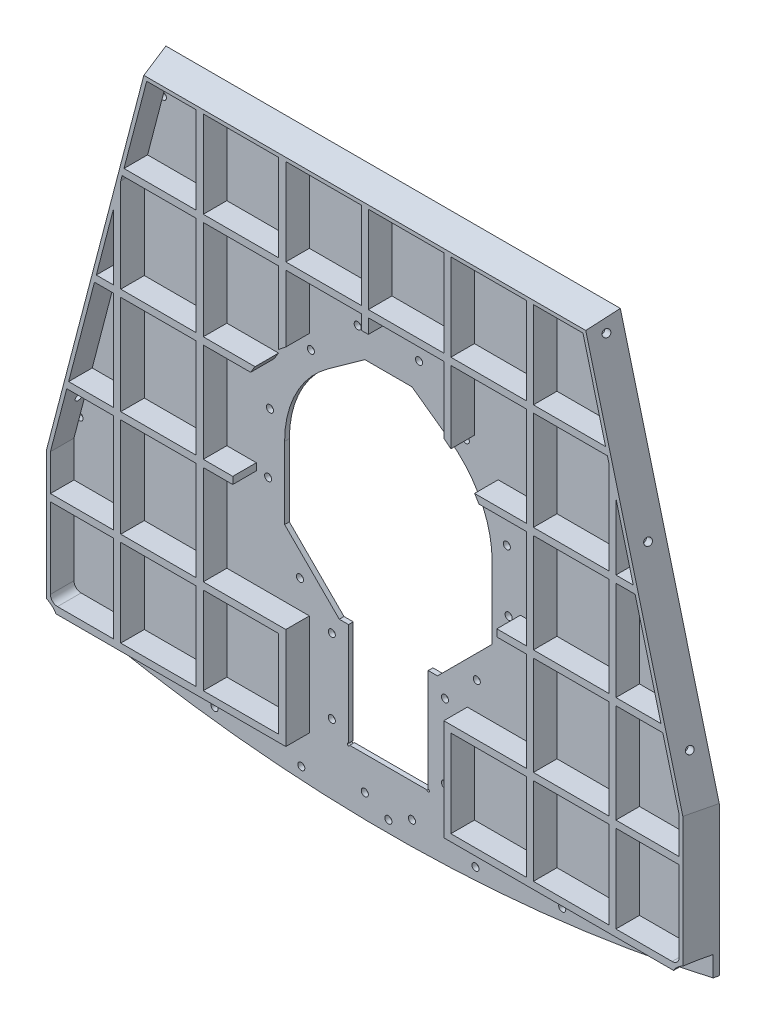
SolidWorks part; units mm, degrees
material "ABS"
ref_plane "前视基准面" through (0, 0, 0) normal (0, 0, 1) x (1, 0, 0)
ref_plane "上视基准面" through (0, 0, 0) normal (0, 1, 0) x (1, 0, 0)
ref_plane "右视基准面" through (0, 0, 0) normal (1, 0, 0) x (0, 0, -1)
other "Configuration Table"
sketch "草图1" plane through (0, 0, 0) normal (0, 0, 1) x (1, 0, 0)
  line L0 (145, -15) -> (145, -95)
  line L1 (145, -95) -> (-145, -95)
  line L2 (-145, -95) -> (-145, -15)
  line L3 (-145, -15) -> (-85, 215)
  line L4 (-85, 215) -> (85, 215)
  line L5 (85, 215) -> (145, -15)
  line L6 (0, 215) -> (0, -95) construction
  arc A0 (145, -95) -> (-145, -95) centre (0, 951.25) cw construction
  point P11 (0, -105)
  dimension "D4" = 320
  dimension "D1" = 10
  dimension "D2" = 290
  dimension "D3" = 80
  dimension "D5" = 170
  dimension "D6" = 95
extrude "凸台-拉伸1" add sketch "草图1" against normal blind 60
chamfer "倒角1" distance 20 distance2 60 4 edges at (115, 100, -60) (145, -55, -60) (-115, 100, -60) (-145, -55, -60)
sketch "草图2" plane through (0, 0, 0) normal (1, 0, 0) x (0, 0, -1)
  line L0 (10, 215) -> (0, 145)
  line L1 (60, 215) -> (0, 215) construction
  line L2 (0, 215) -> (0, -15) construction
  line L3 (0, 145) -> (0, 215)
  line L4 (0, 215) -> (10, 215)
  dimension "D1" = 70
  dimension "D2" = 10
extrude "切除-拉伸1" cut sketch "草图2" against normal through all and the other way through all
chamfer "倒角2" distance 20 distance2 60 1 edges at (0, 215, -60)
sketch "草图16" plane through (0, 0, -60) normal (0, 0, -1) x (-1, 0, 0)
  line L1 (-198.0208, 219.8054) -> (198.0208, 219.8054)
  line L2 (-198.0208, 219.8054) -> (-198.0208, -219.8054)
  line L3 (-198.0208, -219.8054) -> (198.0208, -219.8054)
  line L4 (198.0208, 219.8054) -> (198.0208, -219.8054)
  line L5 (-198.0208, 219.8054) -> (198.0208, -219.8054) construction
  line L6 (-198.0208, -219.8054) -> (198.0208, 219.8054) construction
  point P0 (0, 0)
extrude "切除-拉伸14" cut sketch "草图16" against normal offset from surface (58 mm away) 2 up to face at (0, 11.6667, 0)
sketch "草图17" plane through (0, 0, -2) normal (0, 0, -1) x (-1, 0, 0)
  line L15 (-138.3333, -89) -> (-138.3333, -99)
  line L17 (103.2609, 145) -> (-103.2609, 145) construction
  line L18 (96.3711, 145) -> (-96.3711, 145)
  line L19 (-138.3333, -99) -> (138.3333, -99)
  line L20 (93.114, 157.4855) -> (138.3333, -15.8553)
  line L21 (-138.3333, -15.8553) -> (-93.114, 157.4855)
  line L22 (138.3333, -15.8553) -> (138.3333, -89)
  line L23 (-138.3333, -89) -> (-138.3333, -15.8553)
  line L24 (138.3333, -89) -> (-138.3333, -89)
  line L25 (96.3711, 145) -> (138.3333, -15.8553)
  line L26 (-138.3333, -15.8553) -> (-96.3711, 145)
  line L27 (138.3333, -15.8553) -> (138.3333, -89)
  line L28 (-138.3333, -89) -> (-138.3333, -15.8553)
  line L29 (138.3333, -89) -> (-138.3333, -89) construction
  line L30 (138.3333, -99) -> (138.3333, -89)
  dimension "D2" = 10
  dimension "D1" = 6
extrude "切除-拉伸15" cut sketch "草图17" against normal blind 5 flip side to cut
sketch "草图19" plane through (0, 0, 0) normal (0, 0, 1) x (1, 0, 0)
  line L0 (0, 145) -> (0, -95) construction
  line L1 (-96.3711, 145) -> (96.3711, 145) construction
  line L2 (-138.3333, -95) -> (138.3333, -95) construction
  line L3 (-138.3333, -95) -> (-138.3333, -15.8553) construction
  line L4 (138.3333, -15.8553) -> (138.3333, -95) construction
  line L5 (-138.3333, -79.1076) -> (138.3333, -79.1076) construction
  line L6 (-138.3333, -79.1076) -> (-138.3333, -95)
  line L7 (-138.3333, -95) -> (138.3333, -95)
  line L8 (138.3333, -95) -> (138.3333, -79.1076)
  line L9 (-36.9344, -88.8716) -> (0, 515) construction
  line L10 (130.971, -7.4412) -> (128.3333, 2.67) construction
  line L11 (128.3333, 2.67) -> (128.3333, -79.1076) construction
  line L13 (96.3711, 145) -> (91.533, 143.7379) construction
  line L14 (130.971, -7.4412) -> (113.3015, 60.292) construction
  line L15 (113.3015, 60.292) -> (95.632, 128.0252) construction
  line L16 (95.632, 128.0252) -> (91.533, 143.7379) construction
  line L17 (96.3711, 145) -> (138.3333, -15.8553) construction
  line L18 (138.3333, -15.8553) -> (128.3333, -18.4639) construction
  line L19 (-44, 27) -> (-44, -3.5784)
  line L20 (-44, -3.5784) -> (-20.8284, -26.75)
  line L21 (-20.8284, -26.75) -> (-16.9, -26.75)
  line L23 (-16.9, -70.85) -> (16.9, -70.85)
  line L24 (16.9, -70.85) -> (16.9, -26.75)
  line L25 (16.9, -26.75) -> (20.8284, -26.75)
  line L26 (20.8284, -26.75) -> (44, -3.5784)
  line L27 (44, -3.5784) -> (44, 27)
  line L29 (-56, 27) -> (-56, -8.549) construction
  line L30 (-56, -8.549) -> (-29, -35.549) construction
  line L31 (-29, -35.549) -> (-29, -90) construction
  line L32 (-29, -90) -> (29, -90) construction
  line L33 (29, -90) -> (29, -35.549) construction
  line L34 (29, -35.549) -> (56, -8.549) construction
  line L35 (56, -8.549) -> (56, 27) construction
  line L37 (-56, 27) -> (56, 27) construction
  line L39 (-16.9, -26.75) -> (-16.9, -70.85)
  line L41 (43, 27) -> (43, -1.75) construction
  line L42 (43, -1.75) -> (20, -24.75) construction
  line L43 (20, -24.75) -> (-20, -24.75) construction
  line L44 (-20, -24.75) -> (-43, -1.75) construction
  line L45 (-43, -1.75) -> (-43, 27) construction
  line L47 (-25.682, 62.7272) -> (-10, 74)
  line L48 (-10, 74) -> (10, 74)
  line L49 (10, 74) -> (25.682, 62.7272)
  line L50 (-38.5777, 67.5926) -> (-15, 90) construction
  line L51 (-15, 90) -> (15, 90) construction
  line L52 (15, 90) -> (38.5777, 67.5926) construction
  line L53 (-24, -33.4779) -> (-24, -90) construction
  line L54 (-51, -6.4779) -> (-24, -33.4779) construction
  line L55 (-51, 27) -> (-51, -6.4779) construction
  line L56 (-35.1333, 63.9683) -> (-13.0031, 85) construction
  line L57 (-13.0031, 85) -> (13.0031, 85) construction
  line L58 (13.0031, 85) -> (35.1333, 63.9683) construction
  line L59 (51, -6.4779) -> (51, 27) construction
  line L60 (24, -33.4779) -> (51, -6.4779) construction
  line L61 (24, -90) -> (24, -33.4779) construction
  line L62 (-32.8449, 66.143) -> (0, 27) construction
  line L63 (0, 27) -> (-50.2252, 35.8561) construction
  arc A0 (-138.3333, -79.1076) -> (138.3333, -79.1076) centre (0, 515) ccw
  circle A4 centre (0, -90) radius 1.5
  circle A8 centre (95.632, 128.0252) radius 1.5
  circle A9 centre (113.3015, 60.292) radius 1.5
  circle A10 centre (130.971, -7.4412) radius 1.5
  circle A11 centre (40, 135) radius 1.5
  circle A12 centre (-40, 135) radius 1.5
  circle A16 centre (-130.971, -7.4412) radius 1.5
  circle A17 centre (-113.3015, 60.292) radius 1.5
  circle A18 centre (-95.632, 128.0252) radius 1.5
  circle A24 centre (0, -90) radius 3 construction
  circle A26 centre (0, 515) radius 605 construction
  circle A27 centre (-36.9344, -88.8716) radius 1.5
  circle A28 centre (-73.731, -85.4904) radius 1.5
  circle A29 centre (-110.2525, -79.8692) radius 1.5
  circle A30 centre (36.9344, -88.8716) radius 1.5
  circle A31 centre (73.731, -85.4904) radius 1.5
  circle A32 centre (110.2525, -79.8692) radius 1.5
  arc A33 (44, 27) -> (25.682, 62.7272) centre (0, 27) ccw
  arc A35 (56, 27) -> (38.5777, 67.5926) centre (0, 27) ccw construction
  circle A36 centre (0, 27) radius 43 construction
  arc A37 (-25.682, 62.7272) -> (-44, 27) centre (0, 27) ccw
  arc A38 (-38.5777, 67.5926) -> (-56, 27) centre (0, 27) ccw construction
  arc A39 (-35.1333, 63.9683) -> (-51, 27) centre (0, 27) ccw construction
  arc A40 (51, 27) -> (35.1333, 63.9683) centre (0, 27) ccw construction
  circle A41 centre (-13.0031, 85) radius 1.5
  circle A42 centre (-32.8449, 66.143) radius 1.5
  circle A43 centre (-50.2252, 35.8561) radius 1.5
  circle A44 centre (-51, 10.261) radius 1.5
  circle A45 centre (-37.5, -19.9779) radius 1.5
  circle A46 centre (-24, -33.4779) radius 1.5
  circle A47 centre (-24, -65) radius 1.5
  circle A48 centre (-10, -85) radius 1.5
  circle A49 centre (10, -85) radius 1.5
  circle A50 centre (24, -65) radius 1.5
  circle A51 centre (24, -33.4779) radius 1.5
  circle A52 centre (37.5, -19.9779) radius 1.5
  circle A53 centre (51, 10.261) radius 1.5
  circle A54 centre (50.2252, 35.8561) radius 1.5
  circle A55 centre (32.8449, 66.143) radius 1.5
  circle A56 centre (13.0031, 85) radius 1.5
  point P48 (0, 515)
  point P50 (0, 515)
  point P69 (0, -90)
  point P70 (0, -70.85)
  dimension "D2" = 3
  dimension "D7" = 70
  dimension "D9" = 80
  dimension "D11" = 12
  dimension "D17" = 40
  dimension "D20" = 610
  dimension "D21" = 5
  dimension "D22" = 4
  dimension "D23" = 6
  dimension "D24" = 51.75
  dimension "D15" = 44.1
  dimension "D19" = 45
  dimension "D27" = 3
  dimension "D1" = 88
  dimension "D10" = 58
  dimension "D12" = 56
  dimension "D16" = 86
  dimension "D26" = 20
  dimension "D29" = 7
  dimension "D31" = 3
  dimension "D32" = 5
  dimension "D33" = 20
  dimension "D34" = 10
  dimension "D3" = 3.5
  dimension "D4" = 5
  dimension "D5" = 10
  dimension "D6" = 10
  dimension "D8" = 10
  dimension "D13" = 117
  dimension "D14" = 33.8
  dimension "D18" = 2
  dimension "D25" = 2
  dimension "D28" = 30
  dimension "D30" = 5
  dimension "D35" = 40
  dimension "D36" = 80
extrude "切除-拉伸17" cut sketch "草图19" against normal blind 3
sketch "草图21" plane through (0, 0, 0) normal (0, 0, 1) x (1, 0, 0)
  circle A0 centre (-16.9, -70.85) radius 0.5
  circle A1 centre (16.9, -70.85) radius 0.5
  dimension "D1" = 1
extrude "切除-拉伸19" cut sketch "草图21" against normal blind 10
sketch "草图22" plane through (0, 0, 0) normal (0, 0, 1) x (1, 0, 0)
  line L0 (-96.3711, 145) -> (96.3711, 145) construction
  line L1 (1.5, -74.8692) -> (-1.5, -74.8692)
  line L2 (1.5, -74.8692) -> (1.5, 140)
  line L3 (1.5, 140) -> (-1.5, 140)
  line L4 (-1.5, -74.8692) -> (-1.5, 140)
  line L5 (1.5, -74.8692) -> (-1.5, 140) construction
  line L6 (1.5, 140) -> (-1.5, -74.8692) construction
  line L7 (36.5, -74.8692) -> (36.5, 140)
  line L8 (0, 145) -> (0, -95) construction
  line L9 (-138.3333, -79.1076) -> (-138.3333, -15.8553) construction
  line L10 (-138.3333, -71.8692) -> (138.3333, -71.8692)
  line L11 (-138.3333, -71.8692) -> (-138.3333, -74.8692)
  line L12 (-138.3333, -74.8692) -> (138.3333, -74.8692)
  line L13 (138.3333, -71.8692) -> (138.3333, -74.8692)
  line L14 (-138.3333, -71.8692) -> (138.3333, -74.8692) construction
  line L15 (-138.3333, -74.8692) -> (138.3333, -71.8692) construction
  line L16 (138.3333, -15.8553) -> (138.3333, -79.1076) construction
  line L17 (36.5, -74.8692) -> (33.5, -74.8692)
  line L18 (33.5, -74.8692) -> (33.5, 140)
  line L19 (36.5, 140) -> (33.5, 140)
  line L20 (71.5, -74.8692) -> (71.5, 140)
  line L21 (71.5, -74.8692) -> (68.5, -74.8692)
  line L22 (68.5, -74.8692) -> (68.5, 140)
  line L23 (71.5, 140) -> (68.5, 140)
  line L24 (106.5, -74.8692) -> (106.5, 140)
  line L25 (106.5, -74.8692) -> (103.5, -74.8692)
  line L26 (103.5, -74.8692) -> (103.5, 140)
  line L27 (106.5, 140) -> (103.5, 140)
  line L40 (96.3711, 145) -> (138.3333, -15.8553)
  line L41 (96.3711, 145) -> (91.533, 143.7379)
  line L42 (138.3333, -15.8553) -> (133.4952, -17.1174)
  line L43 (91.533, 143.7379) -> (133.4952, -17.1174)
  line L44 (138.3333, -79.1076) -> (138.3333, -15.8553)
  line L45 (138.3333, -79.1076) -> (133.3333, -79.1076)
  line L46 (138.3333, -15.8553) -> (133.3333, -15.8553)
  line L47 (133.3333, -79.1076) -> (133.3333, -15.8553)
  line L49 (-96.3711, 145) -> (96.3711, 145)
  line L50 (-96.3711, 145) -> (-96.3711, 140)
  line L51 (-96.3711, 140) -> (96.3711, 140)
  line L52 (96.3711, 145) -> (96.3711, 140)
  line L53 (-96.3711, 145) -> (96.3711, 140) construction
  line L54 (-96.3711, 140) -> (96.3711, 145) construction
  line L114 (141.5, -74.8692) -> (141.5, 140) [skipped]
  line L115 (141.5, 140) -> (138.5, 140) [skipped]
  line L116 (176.5, -74.8692) -> (176.5, 140) [skipped]
  line L117 (176.5, -74.8692) -> (173.5, -74.8692) [skipped]
  line L118 (173.5, -74.8692) -> (173.5, 140) [skipped]
  line L119 (176.5, 140) -> (173.5, 140) [skipped]
  line L120 (211.5, -74.8692) -> (211.5, 140) [skipped]
  line L121 (211.5, -74.8692) -> (208.5, -74.8692) [skipped]
  line L122 (208.5, -74.8692) -> (208.5, 140) [skipped]
  line L123 (211.5, 140) -> (208.5, 140) [skipped]
  line L124 (138.5, -74.8692) -> (138.5, 140) [skipped]
  line L125 (141.5, -74.8692) -> (138.5, -74.8692) [skipped]
  line L126 (1.5, 10.1308) -> (1.5, 13.1308)
  line L131 (1.5, 10.1308) -> (133.3333, 10.1308)
  line L132 (133.3333, 10.1308) -> (133.3333, 13.1308)
  line L137 (1.5, 13.1308) -> (133.3333, 13.1308)
  line L138 (1.5, 55.1308) -> (1.5, 58.1308)
  line L139 (1.5, -34.8692) -> (133.3333, -34.8692)
  line L140 (1.5, -34.8692) -> (1.5, -31.8692)
  line L141 (1.5, -31.8692) -> (133.3333, -31.8692)
  line L142 (133.3333, -34.8692) -> (133.3333, -31.8692)
  line L143 (1.5, -34.8692) -> (133.3333, -31.8692) construction
  line L144 (1.5, -31.8692) -> (133.3333, -34.8692) construction
  line L145 (1.5, 55.1308) -> (133.3333, 55.1308)
  line L146 (133.3333, 55.1308) -> (133.3333, 58.1308)
  line L147 (1.5, 58.1308) -> (133.3333, 58.1308)
  line L148 (1.5, 100.1308) -> (1.5, 103.1308)
  line L149 (1.5, 100.1308) -> (133.3333, 100.1308)
  line L150 (133.3333, 100.1308) -> (133.3333, 103.1308)
  line L151 (1.5, 103.1308) -> (133.3333, 103.1308)
  line L232 (-29.3137, -35.2353) -> (-29.3137, -82.85)
  line L233 (-29.3137, -82.85) -> (29.3137, -82.85)
  line L234 (29.3137, -82.85) -> (29.3137, -35.2353)
  line L235 (-56, -8.549) -> (-29.3137, -35.2353)
  line L236 (29.3137, -35.2353) -> (56, -8.549)
  line L237 (56, -8.549) -> (56, 27)
  line L238 (32.6862, 72.471) -> (13.8655, 86)
  line L239 (13.8655, 86) -> (-13.8655, 86)
  line L240 (-13.8655, 86) -> (-32.6862, 72.471)
  line L241 (-56, 27) -> (-56, -8.549)
  line L242 (-56, -8.549) -> (-29.3137, -35.2353)
  line L243 (29.3137, -35.2353) -> (56, -8.549)
  line L244 (56, -8.549) -> (56, 27)
  line L245 (32.6862, 72.471) -> (13.8655, 86)
  line L246 (13.8655, 86) -> (-13.8655, 86)
  line L247 (-13.8655, 86) -> (-32.6862, 72.471)
  line L248 (-56, 27) -> (-56, -8.549)
  line L250 (-16.4, -70.85) -> (16.4, -70.85) construction
  arc A0 (-138.3333, -79.1076) -> (138.3333, -79.1076) centre (0, 515) ccw construction
  circle A3 centre (-110.2525, -79.8692) radius 1.5 construction
  arc A50 (56, 27) -> (32.6862, 72.471) centre (0, 27) ccw
  arc A51 (-32.6862, 72.471) -> (-56, 27) centre (0, 27) ccw
  arc A52 (56, 27) -> (32.6862, 72.471) centre (0, 27) ccw
  arc A53 (-32.6862, 72.471) -> (-56, 27) centre (0, 27) ccw
  point P4 (0, 32.5654)
  point P16 (0, -73.3692)
  point P61 (0, 142.5)
  point P63 (67.4167, -33.3692)
  dimension "D3" = 5
  dimension "D1" = 3
  dimension "D2" = 3
  dimension "D4" = 5
  dimension "D6" = 35
  dimension "D7" = 5
  dimension "D8" = 5
  dimension "D11" = 40
  dimension "D12" = 4
  dimension "D13" = 3
  dimension "D14" = 45
  dimension "D10" = 12
  dimension "D9" = 12
  dimension "D5" = 7
extrude "凸台-拉伸6" add sketch "草图22" along normal blind 10
mirror "镜向1" about plane through (0, 0, 0) normal (1, 0, 0) of "凸台-拉伸6"
sketch "草图24" plane through (0, 0, 10) normal (0, 0, 1) x (1, 0, 0)
  line L0 (-1.5, 86) -> (-1.5, 100.1308) construction
  line L1 (1.5, 86) -> (-1.5, 86)
  line L2 (1.5, 86) -> (1.5, 94)
  line L3 (1.5, 94) -> (-1.5, 94)
  line L4 (-1.5, 86) -> (-1.5, 94)
  line L5 (1.5, 86) -> (-1.5, 94) construction
  line L6 (1.5, 94) -> (-1.5, 86) construction
  circle A0 centre (138.3333, -79.1076) radius 8.5
  circle A1 centre (-138.3333, -79.1076) radius 8.5
  point P4 (0, 90)
  dimension "D2" = 17
  dimension "D3" = 17
  dimension "D1" = 8
extrude "切除-拉伸20" cut sketch "草图24" against normal up to surface (10 mm away) up to face at (0, 24.8246, 0)
chamfer "倒角4" distance 12 angle 16 5 edges at (-138.3333, -43.2314, 10) (-117.3522, 64.5724, 10) (0, 145, 10) (117.3522, 64.5724, 10) (138.3333, -43.2314, 10)
fillet "圆角2" radius 3 2 edges at (-133.3333, -71.8692, 5) (133.3333, -71.8692, 5)
sketch "草图28" plane through (115.5877, 30.1533, 34.2535) normal (0.9301, 0.2426, 0.2756) x (0.2667, 0.0696, -0.9613)
  circle A1 centre (31.6689, -30.0555) radius 1.5
  circle A4 centre (31.6689, 109.9445) radius 1.5
  circle A6 centre (31.6689, 39.9445) radius 1.5
extrude "切除-拉伸22" cut sketch "草图28" against normal blind 5
mirror "镜向2" about plane through (0, 0, 0) normal (1, 0, 0) of "切除-拉伸22"
